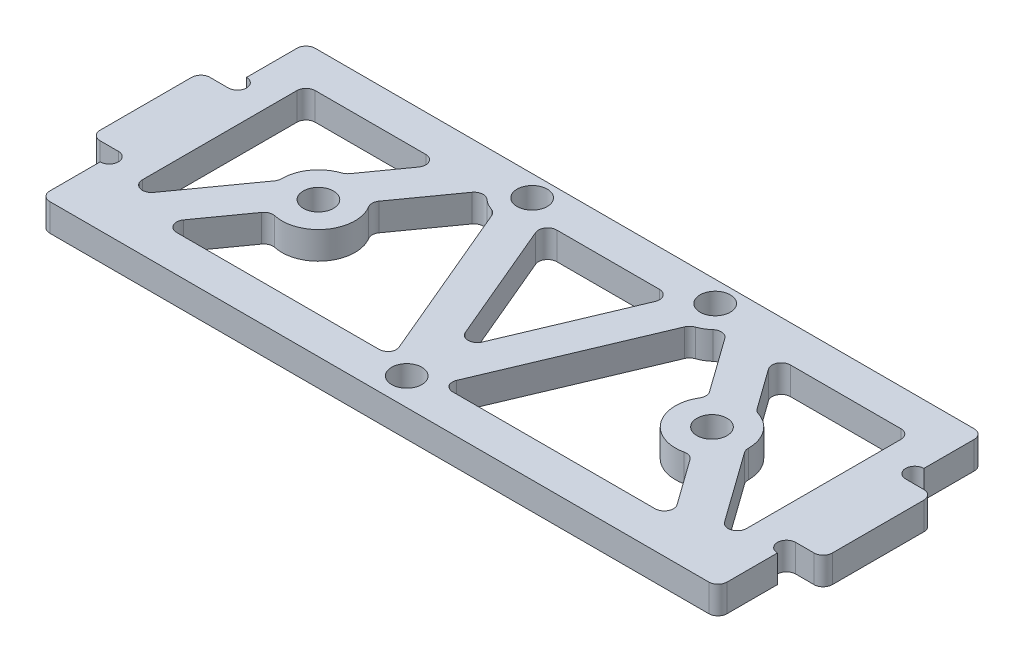
SolidWorks part; units mm, degrees
material "Thornel Mat VMA"
ref_plane "前视基准面" through (0, 0, 0) normal (0, 0, 1) x (1, 0, 0)
ref_plane "上视基准面" through (0, 0, 0) normal (0, 1, 0) x (1, 0, 0)
ref_plane "右视基准面" through (0, 0, 0) normal (1, 0, 0) x (0, 0, -1)
sketch "草图3" plane through (0, 0, 0) normal (0, 1, 0) x (1, 0, 0)
  line L0 (-37, -20.5) -> (-40, -20.5)
  line L1 (-40, -20.5) -> (-40, -8.5)
  line L2 (-10, -2.3) -> (10, -2.3) construction
  line L3 (0, -2.3) -> (0, -26) construction
  line L4 (0, -14.15) -> (-21.5, -14.15) construction
  line L5 (-40, -8.5) -> (-37, -8.5)
  line L6 (-37, 0) -> (37, 0)
  line L7 (-37, -20.5) -> (-37, -29)
  line L8 (-37, -29) -> (37, -29)
  line L10 (-37, -8.5) -> (-37, 0)
  line L11 (0, -1.65) -> (0, 1.65) construction
  line L12 (37, -8.5) -> (37, 0)
  line L13 (37, -20.5) -> (37, -29)
  line L14 (40, -8.5) -> (37, -8.5)
  line L15 (40, -20.5) -> (40, -8.5)
  line L16 (37, -20.5) -> (40, -20.5)
  circle A2 centre (-10, -2.3) radius 1.65
  circle A3 centre (10, -2.3) radius 1.65
  circle A4 centre (0, -26) radius 1.65
  circle A5 centre (-21.5, -14.15) radius 1.65
  circle A6 centre (21.5, -14.15) radius 1.65
  dimension "D1" = 29
  dimension "D2" = 74
  dimension "D6" = 3.3
  dimension "D7" = 12
  dimension "D9" = 21.5
  dimension "D3" = 23.7
  dimension "D4" = 20
  dimension "D5" = 2.3
  dimension "D8" = 3
extrude "凸台-拉伸6" add sketch "草图3" along normal blind 3
sketch "草图4" plane through (0, 3, 0) normal (0, 1, 0) x (1, 0, 0)
  line L0 (-37, 0) -> (-37, -8.5) construction
  line L1 (-37, -20.5) -> (-37, -29) construction
  line L2 (37, 0) -> (-37, 0) construction
  line L3 (-33, -4) -> (-17.9775, -4)
  line L4 (-28.0819, -25) -> (-22.9789, -17.8666)
  line L5 (-10.7261, -5.7239) -> (-2.9593, -24.1311)
  line L6 (-3.3541, -25) -> (-28.0819, -25)
  line L7 (-33, -25) -> (-33, -4)
  line L8 (-7.112, -4) -> (7.112, -4)
  line L10 (0, -20.8553) -> (-7.112, -4)
  line L11 (-18.4603, -11.5499) -> (-13.0594, -4)
  line L12 (-37, -29) -> (37, -29) construction
  line L13 (-10, -2.3) -> (0, -26) construction
  line L14 (0, -1.65) -> (0, 1.65) construction
  line L15 (0, -20.8553) -> (7.112, -4)
  line L16 (33, -25) -> (33, -4)
  line L17 (3.3541, -25) -> (28.0819, -25)
  line L18 (10.7261, -5.7239) -> (2.9593, -24.1311)
  line L20 (-17.9775, -4) -> (-22.4607, -10.2671)
  line L21 (33, -4) -> (17.9775, -4)
  line L22 (28.0819, -25) -> (22.9789, -17.8666)
  line L23 (17.9775, -4) -> (22.4607, -10.2671)
  line L24 (18.4603, -11.5499) -> (13.0594, -4)
  line L25 (-25.4851, -14.4949) -> (-33, -25)
  line L26 (25.4851, -14.4949) -> (33, -25)
  circle A0 centre (-37, -7.5) radius 1
  circle A1 centre (-37, -21.5) radius 1
  arc A4 (-13.0594, -4) -> (-10.7261, -5.7239) centre (-10, -2.3) ccw
  arc A5 (-2.9593, -24.1311) -> (-3.3541, -25) centre (0, -26) ccw
  circle A6 centre (37, -21.5) radius 1
  circle A7 centre (37, -7.5) radius 1
  arc A8 (2.9593, -24.1311) -> (3.3541, -25) centre (0, -26) cw
  arc A9 (13.0594, -4) -> (10.7261, -5.7239) centre (10, -2.3) cw
  arc A10 (-22.9789, -17.8666) -> (-18.4603, -11.5499) centre (-21.5, -14.15) ccw
  arc A11 (22.9789, -17.8666) -> (18.4603, -11.5499) centre (21.5, -14.15) cw
  arc A12 (-22.4607, -10.2671) -> (-25.4851, -14.4949) centre (-21.5, -14.15) ccw
  arc A13 (22.4607, -10.2671) -> (25.4851, -14.4949) centre (21.5, -14.15) cw
  dimension "D1" = 2
  dimension "D7" = 3.5
  dimension "D8" = 4
  dimension "D9" = 8
  dimension "D2" = 4
  dimension "D3" = 4
  dimension "D4" = 4
  dimension "D5" = 4
  dimension "D6" = 2
extrude "切除-拉伸1" cut sketch "草图4" against normal through all
other "移动面1" [suppressed] offset 1 parameters "D1"=1
fillet "圆角1" radius 1 35 edges at (-37, 1.5, 0) (37, 1.5, 0) (40, 1.5, 8.5) (40, 1.5, 20.5) (37, 1.5, 29) (-37, 1.5, 29) (-40, 1.5, 20.5) (-40, 1.5, 8.5) (17.9775, 1.5, 4) (33, 1.5, 4) (2.9593, 1.5, 24.1311) (10.7261, 1.5, 5.7239) (13.0594, 1.5, 4) (18.4603, 1.5, 11.5499) (22.9789, 1.5, 17.8666) (28.0819, 1.5, 25) (3.3541, 1.5, 25) (-28.0819, 1.5, 25) (-18.4603, 1.5, 11.5499) (-13.0594, 1.5, 4) (-10.7261, 1.5, 5.7239) (-2.9593, 1.5, 24.1311) (-3.3541, 1.5, 25) (-33, 1.5, 4) (-17.9775, 1.5, 4) (-7.112, 1.5, 4) (7.112, 1.5, 4) (0, 1.5, 20.8553) (-22.9789, 1.5, 17.8666) (33, 1.5, 25) (25.4851, 1.5, 14.4949) (22.4607, 1.5, 10.2671) (-22.4607, 1.5, 10.2671) (-25.4851, 1.5, 14.4949) (-33, 1.5, 25)
